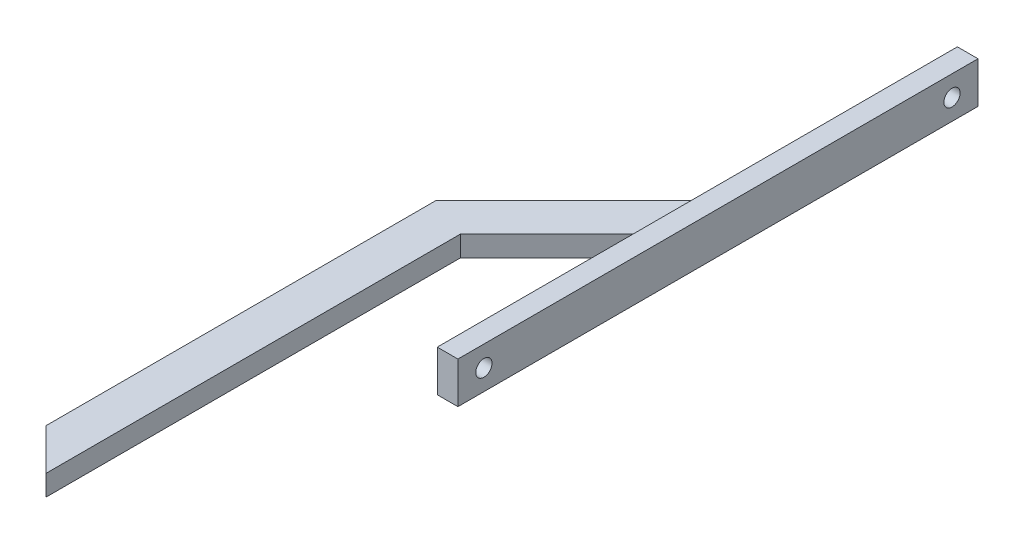
SolidWorks part; units mm, degrees
ref_plane "Front Plane" through (0, 0, 0) normal (0, 0, 1) x (1, 0, 0)
ref_plane "Top Plane" through (0, 0, 0) normal (0, 1, 0) x (1, 0, 0)
ref_plane "Right Plane" through (0, 0, 0) normal (1, 0, 0) x (0, 0, -1)
sketch "Sketch2" plane through (0, 0, 0) normal (0, 0, 1) x (1, 0, 0)
  line L1 (-3.175, -6.35) -> (3.175, -6.35)
  line L2 (-3.175, -6.35) -> (-3.175, 6.35)
  line L3 (-3.175, 6.35) -> (3.175, 6.35)
  line L4 (3.175, -6.35) -> (3.175, 6.35)
  line L5 (-3.175, -6.35) -> (3.175, 6.35) construction
  line L6 (-3.175, 6.35) -> (3.175, -6.35) construction
  point P0 (0, 0)
  dimension "D1" = 6.35
  dimension "D2" = 12.7
extrude "Boss-Extrude1" add sketch "Sketch2" along normal blind 80 and the other way blind 80
sketch "Sketch4" plane through (3.175, 0, 0) normal (1, 0, 0) x (0, 0, -1)
  line L0 (0, 0) -> (0, -6.35) construction
  line L1 (80, -6.35) -> (-80, -6.35) construction
  line L2 (-80, -6.35) -> (-80, 6.35) construction
  circle A0 centre (-72, 0) radius 2.5
  circle A1 centre (72, 0) radius 2.5
  dimension "D1" = 5
  dimension "D2" = 8
extrude "Cut-Extrude1" cut sketch "Sketch4" against normal through all
sketch "Sketch5" plane through (0, 0, 0) normal (0, 1, 0) x (0, 0, -1)
  line L0 (80, -3.175) -> (-80, -3.175) construction
  line L5 (-4.4901, -5.8053) -> (4.4901, 3.175) construction
  line L6 (4.4901, 3.175) -> (-37.9363, 45.6014)
  line L7 (-37.9363, 45.6014) -> (-46.9165, 36.6212) construction
  line L8 (-46.9165, 36.6212) -> (-4.4901, -5.8053) construction
  line L9 (-37.9363, 45.6014) -> (-4.4901, -5.8053) construction
  line L10 (-46.9165, 36.6212) -> (4.4901, 3.175) construction
  line L11 (80, 3.175) -> (-80, 3.175) construction
  line L12 (-37.9363, 45.6014) -> (-157.9363, 45.6014)
  line L13 (-157.9363, 45.6014) -> (-170.6363, 32.9014)
  line L14 (-170.6363, 32.9014) -> (-43.1968, 32.9014)
  line L16 (4.4901, 3.175) -> (-1.8599, -3.175)
  line L17 (-1.8599, -3.175) -> (-7.1204, -3.175)
  line L18 (-7.1204, -3.175) -> (-43.1968, 32.9014)
  point P7 (-21.2132, 19.8981)
  point P8 (-21.2132, 19.8981)
  point P9 (0, -1.3151)
  dimension "D1" = 45
  dimension "D2" = 12.7
  dimension "D3" = 60
  dimension "D4" = 12.7
  dimension "D5" = 45
  dimension "D6" = 120
extrude "Boss-Extrude2" add sketch "Sketch5" along normal blind 3.175 and the other way blind 3.175
